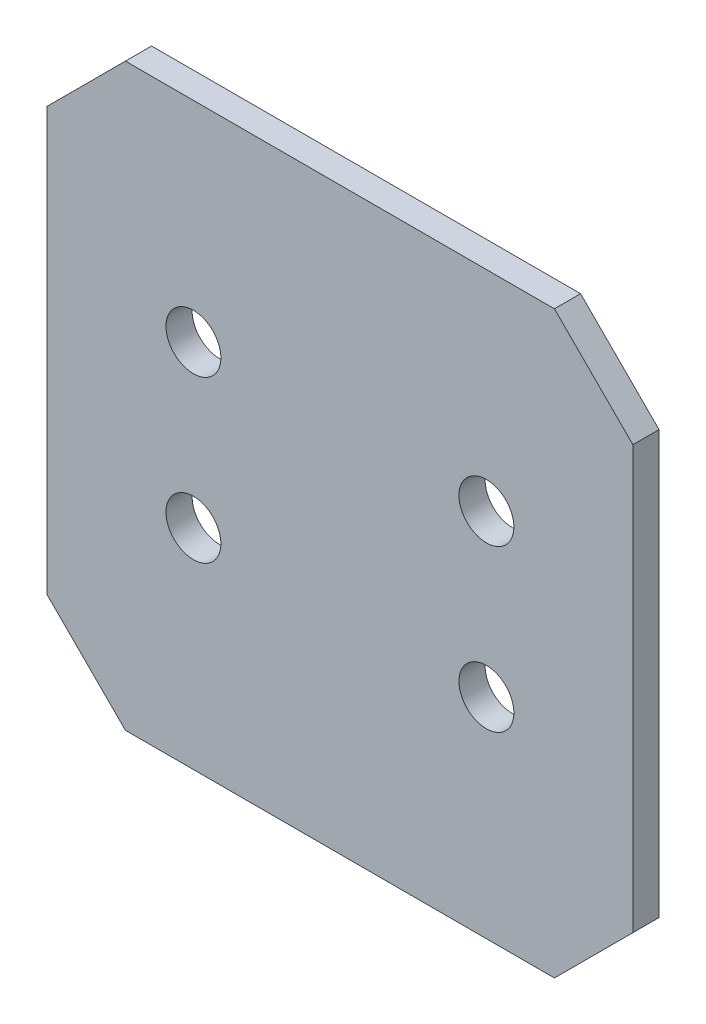
SolidWorks part; units mm, degrees
note: The reader was unsure of these and kept them because the rebuilt part matched: thickness of "Базовая кромка1", "Листовой металл3".
material "AISI 1020"
ref_plane "Спереди" through (0, 0, 0) normal (0, 0, 1) x (1, 0, 0)
ref_plane "Сверху" through (0, 0, 0) normal (0, 1, 0) x (1, 0, 0)
ref_plane "Справа" through (0, 0, 0) normal (1, 0, 0) x (0, 0, -1)
sketch "Эскиз1" plane through (0, 0, 0) normal (0, 0, 1) x (1, 0, 0)
  line L0 (0, -1000) -> (0, 49000) construction
  line L1 (56, 3) -> (-56, 3)
  line L2 (-530.3264, 86.7738) -> (144.1634, 86.7738) construction
  line L3 (-56, 3) -> (-56, 113.7738)
  line L5 (-537.2086, 113.7738) -> (144.1634, 113.7738) construction
  line L6 (-56, 113.7738) -> (56, 113.7738)
  line L7 (133.9446, 3) -> (-133.9446, 3) construction
  line L8 (133.9446, 3) -> (-133.9446, 3) construction
  line L9 (-15, 30) -> (-15, 86.7738) construction
  line L10 (164.1634, 30) -> (-740.8168, 30) construction
  line L11 (0, 73.7738) -> (-56, 73.7738) construction
  line L12 (56, 3) -> (56, 113.7738)
  circle A0 centre (-28, 73.7738) radius 5.25
  circle A1 centre (-28, 73.7738) radius 13 construction
  circle A2 centre (-28, 43) radius 5.25
  circle A3 centre (-28, 43) radius 13 construction
  circle A4 centre (28, 73.7738) radius 5.25
  circle A5 centre (28, 43) radius 5.25
  point P27 (-28, 73.7738)
  point P33 (0, 3)
  point P34 (0, 113.7738)
  dimension "D1" = 10.5
  dimension "D2" = 26
base flange "Базовая кромка1" sketch "Эскиз1" thickness 5 reverse thickness direction no parameters "D1"=0.74
chamfer "Фаска1" distance 15 angle 45 4 edges at (56, 3, -2.5) (-56, 3, -2.5) (56, 113.7738, -2.5) (-56, 113.7738, -2.5)
sketch "Сгиб-Линии1" [suppressed] plane through (0, 0, 0) normal (0, 1, 0) x (1, 0, 0)
sketch "Граничная рамка1" [suppressed] plane through (0, 0, 0) normal (0, 1, 0) x (1, 0, 0)
sheet metal parameters "Листовой металл3" thickness 5 parameters "D1"=0.74, "D7"=4
flat pattern "Развертка3" [suppressed]
sketch "Сгиб-Линии2" plane through (0, 0, 0) normal (0, 1, 0) x (1, 0, 0)
sketch3d "Граничная рамка2" [suppressed]
  line L0 (-56, 3, 0) -> (56, 3, 0) construction
  line L1 (-56, 113.7738, 0) -> (56, 113.7738, 0) construction
  line L2 (-56, 3, 0) -> (-56, 113.7738, 0) construction
  line L3 (56, 3, 0) -> (56, 113.7738, 0) construction
